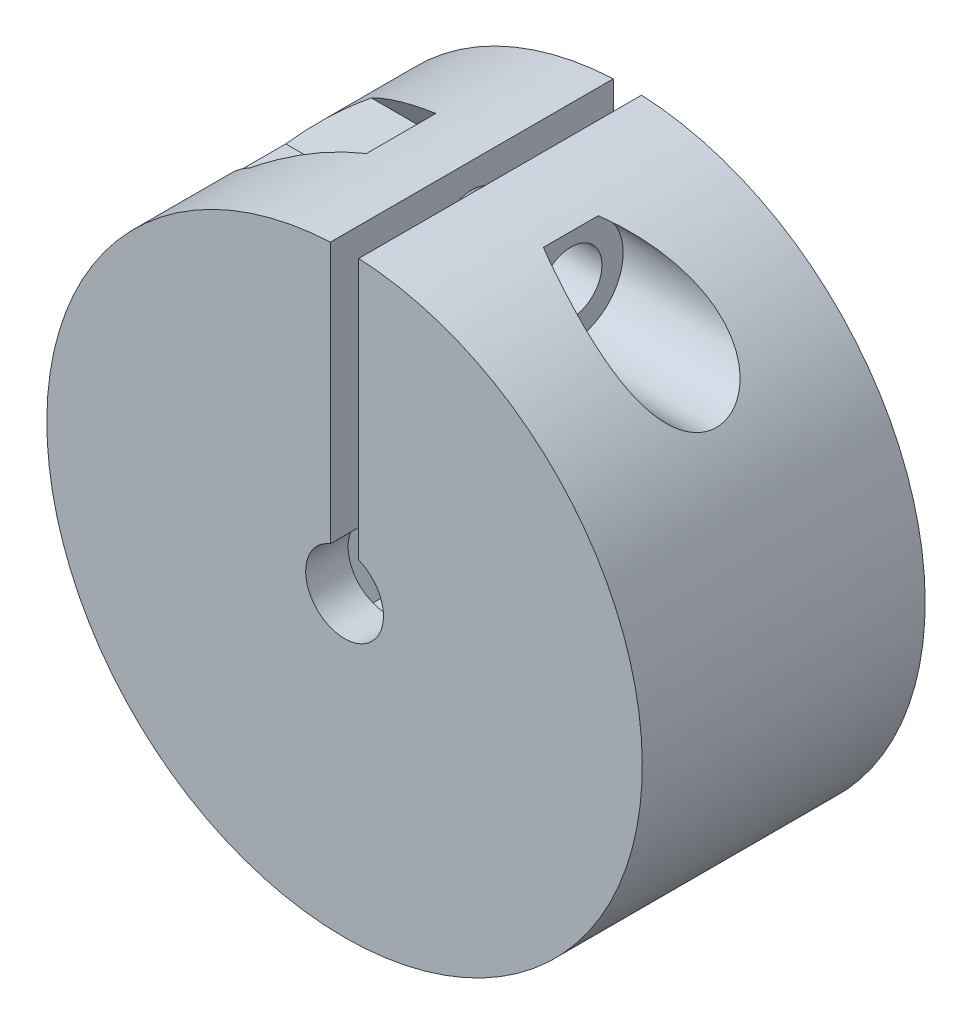
SolidWorks part; units mm, degrees
ref_plane "Piano frontale" through (0, 0, 0) normal (0, 0, 1) x (1, 0, 0)
ref_plane "Piano superiore" through (0, 0, 0) normal (0, 1, 0) x (1, 0, 0)
ref_plane "Piano destro" through (0, 0, 0) normal (1, 0, 0) x (0, 0, -1)
sketch "Schizzo1" plane through (0, 0, 0) normal (0, 0, 1) x (1, 0, 0)
  circle A0 centre (0, 0) radius 6.05
  circle A1 centre (0, 0) radius 21.05
  dimension "D1" = 12.1
  dimension "D2" = 15
extrude "Estrusione-Estrusione1" add sketch "Schizzo1" along normal blind 20
sketch "Schizzo6" plane through (0, 0, 20) normal (0, 0, 1) x (1, 0, 0)
  line L1 (2.4703, 4.0387) -> (-2.2625, 4.1587)
  line L2 (-2.2625, 4.1587) -> (-4.7328, 0.12)
  line L3 (-4.7328, 0.12) -> (-2.4703, -4.0387)
  line L4 (-2.4703, -4.0387) -> (2.2625, -4.1587)
  line L5 (2.2625, -4.1587) -> (4.7328, -0.12)
  line L6 (4.7328, -0.12) -> (2.4703, 4.0387)
  circle A0 centre (0, 0) radius 4.1 construction
  circle A1 centre (0, 0) radius 6.05
  circle A2 centre (0, 0) radius 6.05 construction
  dimension "D1" = 8.2
extrude "Estrusione-Estrusione2" add sketch "Schizzo6" against normal blind 8
sketch "Schizzo8" plane through (0, 0, 20) normal (0, 0, 1) x (1, 0, 0)
  line L1 (-2.2625, 4.1587) -> (-4.7328, 0.12) construction
  line L2 (-4.7328, 0.12) -> (-2.4703, -4.0387) construction
  line L3 (-2.4703, -4.0387) -> (2.2625, -4.1587) construction
  line L4 (2.2625, -4.1587) -> (4.7328, -0.12) construction
  line L5 (4.7328, -0.12) -> (2.4703, 4.0387) construction
  line L6 (2.4703, 4.0387) -> (-2.2625, 4.1587) construction
  line L7 (-2.2625, 4.1587) -> (-4.7328, 0.12)
  line L8 (-4.7328, 0.12) -> (-2.4703, -4.0387)
  line L9 (-2.4703, -4.0387) -> (2.2625, -4.1587)
  line L10 (2.2625, -4.1587) -> (4.7328, -0.12)
  line L11 (4.7328, -0.12) -> (2.4703, 4.0387)
  line L12 (2.4703, 4.0387) -> (-2.2625, 4.1587)
  circle A0 centre (0, 0) radius 2.75
  dimension "D1" = 5.5
extrude "Estrusione-Estrusione3" add sketch "Schizzo8" against normal blind 3
sketch "Schizzo2" plane through (0, 0, 20) normal (0, 0, 1) x (1, 0, 0)
  line L0 (0, 0) -> (0, 21.05) construction
  line L2 (1, 0.9503) -> (-1, 0.9503)
  line L3 (1, 0.9503) -> (1, 25.8538)
  line L4 (1, 25.8538) -> (-1, 25.8538)
  line L5 (-1, 0.9503) -> (-1, 25.8538)
  line L6 (1, 0.9503) -> (-1, 25.8538) construction
  line L7 (1, 25.8538) -> (-1, 0.9503) construction
  circle A0 centre (0, 0) radius 21.05 construction
  point P6 (0, 13.402)
  point P11 (0, 8.1548)
  point P13 (0, 7)
  point P14 (0, 0)
  point P15 (0, 11.432)
  dimension "D1" = 2
extrude "Taglio-Estrusione1" cut sketch "Schizzo2" against normal blind 20
sketch "Schizzo3" plane through (1, 0, 0) normal (-1, 0, 0) x (0, 0, 1)
  line L0 (10, 21.0262) -> (10, -21.05) construction
  line L1 (20, 21.0262) -> (0, 21.0262) construction
  line L2 (0, -21.05) -> (20, -21.05) construction
  line L3 (0, 17.0262) -> (20, 17.0262) construction
  line L4 (0, 21.0262) -> (0, -21.05) construction
  line L5 (20, -21.05) -> (20, 21.0262) construction
  circle A0 centre (10, 17.0262) radius 2.2
  point P14 (10, 9.9642)
  point P15 (10, 9.2114)
  dimension "D2" = 4.4
  dimension "D1" = 4
extrude "Taglio-Estrusione2" cut sketch "Schizzo3" against normal through all both and the other way through all
sketch "Schizzo4" plane through (1, 0, 0) normal (-1, 0, 0) x (0, 0, 1)
  circle A0 centre (10, 17.0262) radius 3.7
  dimension "D1" = 7.4
extrude "Taglio-Estrusione3" cut sketch "Schizzo4" against normal blind 20 from offset 5 offset against normal yes
sketch "Schizzo5" plane through (-1, 0, 0) normal (1, 0, 0) x (0, 0, -1)
  line L1 (-7.8638, 20.7262) -> (-12.1362, 20.7262)
  line L2 (-12.1362, 20.7262) -> (-14.2724, 17.0262)
  line L3 (-14.2724, 17.0262) -> (-12.1362, 13.3262)
  line L4 (-12.1362, 13.3262) -> (-7.8638, 13.3262)
  line L5 (-7.8638, 13.3262) -> (-5.7276, 17.0262)
  line L6 (-5.7276, 17.0262) -> (-7.8638, 20.7262)
  circle A0 centre (-10, 17.0262) radius 3.7 construction
  dimension "D1" = 7.4
extrude "Taglio-Estrusione4" cut sketch "Schizzo5" against normal blind 20 from offset 5 offset against normal yes
chamfer "Smusso1" distance 1 angle 45 1 edges at (0, -6.05, 0)
